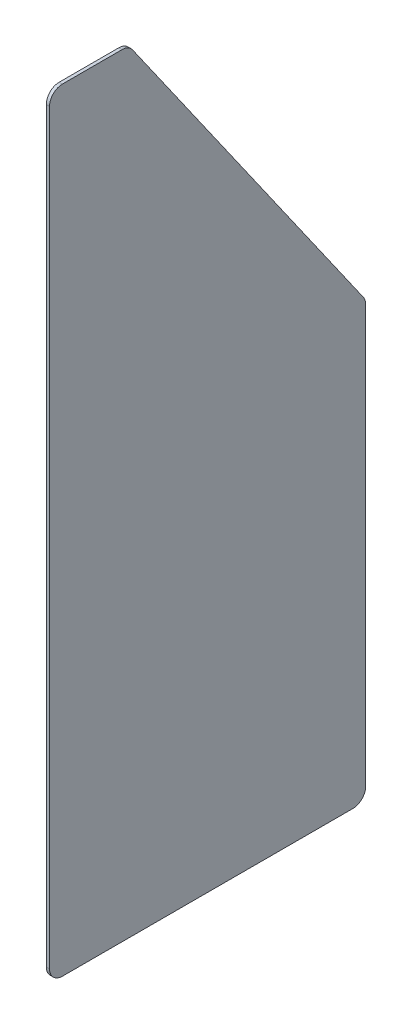
SolidWorks part; units mm, degrees
ref_plane "Front Plane" through (0, 0, 0) normal (0, 0, 1) x (1, 0, 0)
ref_plane "Top Plane" through (0, 0, 0) normal (0, 1, 0) x (1, 0, 0)
ref_plane "Right Plane" through (0, 0, 0) normal (1, 0, 0) x (0, 0, -1)
sketch "Sketch1" plane through (0, 0, 0) normal (0, 1, 0) x (1, 0, 0)
  line L4 (1.5875, 155.8925) -> (0, 155.8925)
  line L5 (0, 155.8925) -> (0, 0)
  line L6 (1.5875, 155.8925) -> (1.5875, 0)
  line L7 (1.5875, 0) -> (0, 0)
  point P3 (0, 0)
  dimension "D1" = 155.8925
  dimension "D4" = 1.5875
extrude "Boss-Extrude1" add sketch "Sketch1" along normal blind 381
sketch "Sketch2" plane through (0, 0, 0) normal (-1, 0, 0) x (0, 0, 1)
  line L0 (-39.0525, 381) -> (-155.8925, 214.122)
  line L1 (-155.8925, 214.122) -> (-155.8925, 381)
  line L2 (-155.8925, 381) -> (-39.0525, 381)
  line L3 (-155.8925, 381) -> (-155.8925, 0) construction
  line L4 (-155.8925, 381) -> (0, 381) construction
  line L5 (0, 381) -> (0, 0) construction
  dimension "D1" = 214.122
  dimension "D2" = 39.0525
extrude "Cut-Extrude1" cut sketch "Sketch2" against normal up to surface (1.5875 mm away) up to face at (1.5875, 190.5, -77.9462)
fillet "Fillet1" radius 6.35 5 edges at (0.7937, 0, -155.8925) (0.7938, 0, 0) (0.7938, 381, 0) (0.7937, 381, -39.0525) (0.7937, 214.122, -155.8925)
